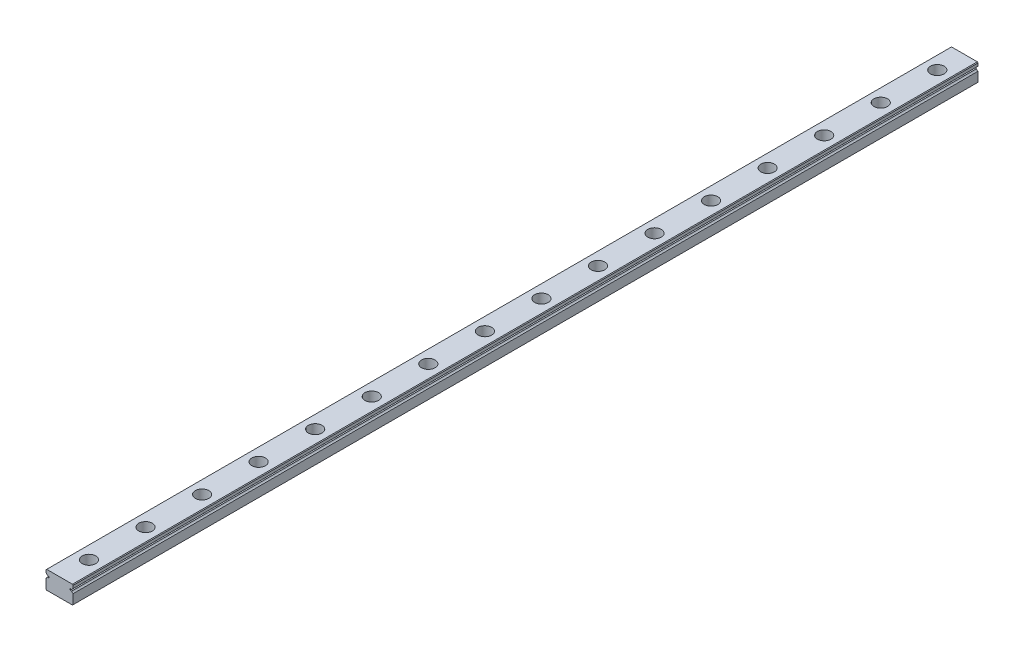
SolidWorks part; units mm, degrees
ref_plane "Спереди" through (0, 0, 0) normal (0, 0, 1) x (1, 0, 0)
ref_plane "Сверху" through (0, 0, 0) normal (0, 1, 0) x (1, 0, 0)
ref_plane "Справа" through (0, 0, 0) normal (1, 0, 0) x (0, 0, -1)
sketch "Эскиз1" plane through (0, 0, 0) normal (0, 0, 1) x (1, 0, 0)
  line L0 (-6, 3.7) -> (-5.7, 4)
  line L1 (-5.7, -4) -> (5.7, -4)
  line L2 (-6, -3.7) -> (-6, 0.549)
  line L3 (-5.7, 4) -> (5.7, 4)
  line L4 (6, -3.7) -> (6, 0.549)
  line L5 (-6, -4) -> (6, 4) construction
  line L6 (-6, 4) -> (6, -4) construction
  line L7 (-6, -3.7) -> (-5.7, -4)
  line L8 (5.7, -4) -> (6, -3.7)
  line L9 (5.7, 4) -> (6, 3.7)
  line L10 (-6, 2.451) -> (-6, 3.7)
  line L11 (-5.3546, 1.7981) -> (-4.6435, 1.7981)
  line L12 (0, 5.4188) -> (0, -5.747) construction
  line L13 (-5.3546, 1.2019) -> (-4.6435, 1.2019)
  line L14 (-4.6435, 1.7981) -> (-4.6435, 1.2019)
  line L15 (4.6435, 1.7981) -> (4.6435, 1.2019)
  line L16 (5.3546, 1.2019) -> (4.6435, 1.2019)
  line L17 (5.3546, 1.7981) -> (4.6435, 1.7981)
  line L18 (6, 2.451) -> (6, 3.7)
  line L19 (4.6435, 1.7981) -> (5.3546, 1.7981) construction
  arc A0 (-6, 0.549) -> (-5.3546, 1.2019) centre (-6.3091, 1.5) ccw
  arc A1 (-5.3546, 1.7981) -> (-6, 2.451) centre (-6.3091, 1.5) ccw
  arc A2 (5.3546, 1.7981) -> (6, 2.451) centre (6.3091, 1.5) cw
  arc A3 (6, 0.549) -> (5.3546, 1.2019) centre (6.3091, 1.5) cw
  point P0 (0, 0)
extrude "Бобышка-Вытянуть1" add sketch "Эскиз1" along normal blind 400
sketch "Эскиз2" plane through (0, 4, 0) normal (0, 1, 0) x (1, 0, 0)
  line L0 (0, 0) -> (0, -26.2396) construction
  line L1 (5.7, 0) -> (-5.7, 0) construction
  line L2 (-3.8306, -12) -> (3.8306, -12) construction
  circle A0 centre (0, -12) radius 3
  circle A1 centre (0, -12) radius 1.75
  dimension "D2" = 3.5
  dimension "D3" = 6
  dimension "D1" = 12
extrude "Вырез-Вытянуть1" cut sketch "Эскиз2" against normal blind 4.5
extrude "Вырез-Вытянуть2" cut sketch "Эскиз2<2>" against normal through all contours A1 region at (0, 4, 12)
sketch "Эскиз2<2>" plane through (0, 4, 0) normal (0, 1, 0) x (1, 0, 0) same geometry as "Эскиз2"
pattern_linear "Линейный массив1" count 16 spacing 25 along (0, 0, 1) of "Вырез-Вытянуть1", "Вырез-Вытянуть2"
